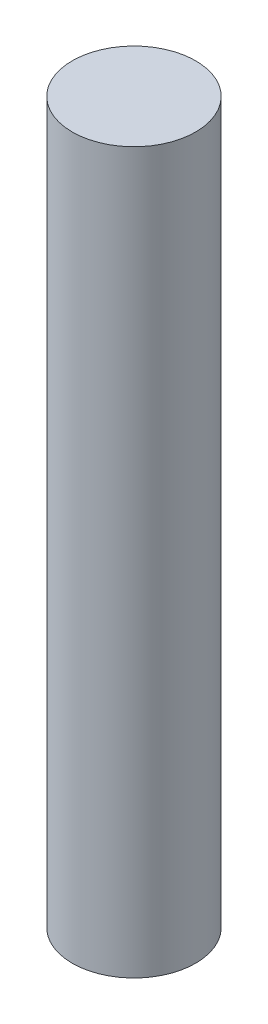
SolidWorks part; units mm, degrees
ref_plane "Front Plane" through (0, 0, 0) normal (0, 0, 1) x (1, 0, 0)
ref_plane "Top Plane" through (0, 0, 0) normal (0, 1, 0) x (1, 0, 0)
ref_plane "Right Plane" through (0, 0, 0) normal (1, 0, 0) x (0, 0, -1)
sketch "Sketch1" plane through (0, 0, 0) normal (0, 1, 0) x (1, 0, 0)
  circle A0 centre (0, 0) radius 3
  dimension "D1" = 6
extrude "Boss-Extrude1" add sketch "Sketch1" along normal blind 35
sketch "Sketch2" plane through (0, 0, 0) normal (0, -1, 0) x (1, 0, 0)
  line L0 (0, -2.5) -> (0, 2) construction
  line L1 (-1.5, 2) -> (1.5, 2)
  arc A0 (-1.5, 2) -> (1.5, 2) centre (0, 0) ccw
  dimension "D1" = 5
  dimension "D2" = 4.5
extrude "Cut-Extrude1" cut sketch "Sketch2" against normal blind 22
sketch "Sketch3" plane through (0, 0, 0) normal (0, -1, 0) x (1, 0, 0)
  circle A0 centre (0, 0) radius 2.5
  dimension "D1" = 5
extrude "Cut-Extrude2" cut sketch "Sketch3" against normal blind 4
